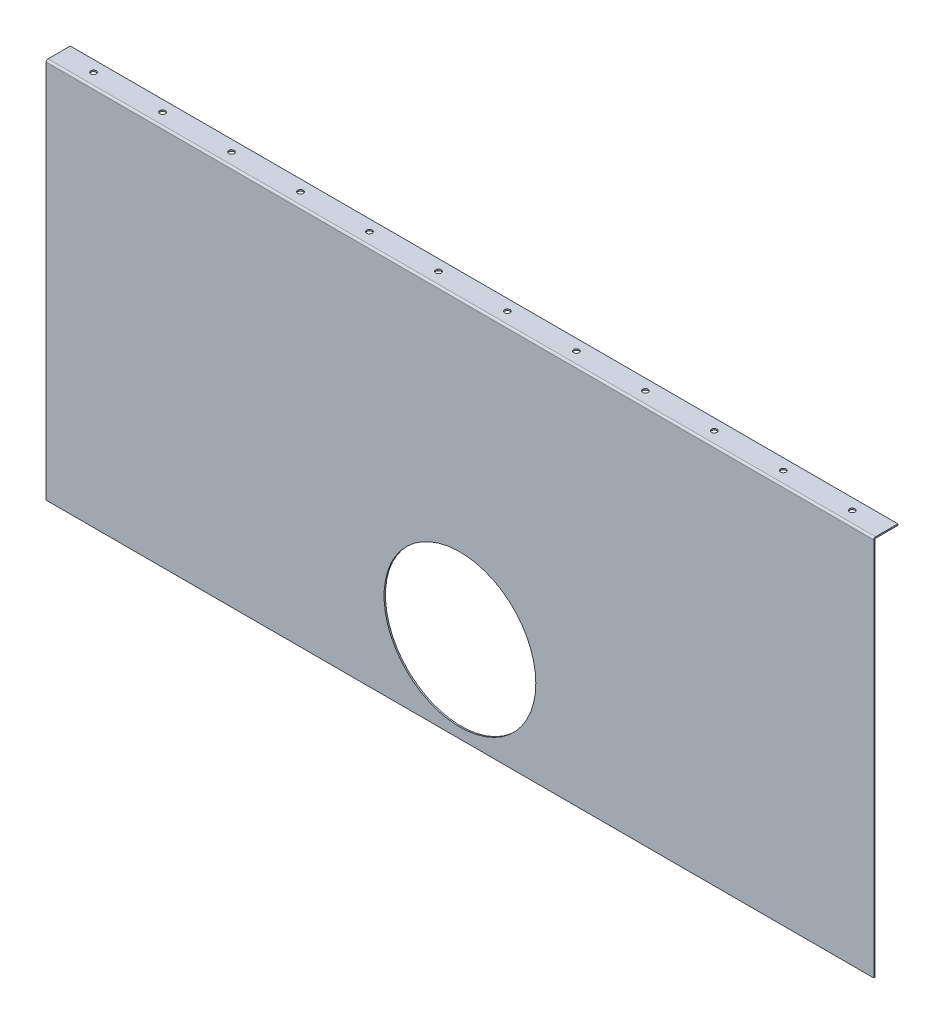
SolidWorks part; units mm, degrees
note: The reader was unsure of these and kept them because the rebuilt part matched: thickness of "Base-Flange1", "Edge-Flange1", "Sheet-Metal1", "Sheet-Metal2", "Sheet-Metal3", "Sheet-Metal4"; flange length of "Edge-Flange1".
material "AISI 304"
ref_plane "Front Plane" through (0, 0, 0) normal (0, 0, 1) x (1, 0, 0)
ref_plane "Top Plane" through (0, 0, 0) normal (0, 1, 0) x (1, 0, 0)
ref_plane "Right Plane" through (0, 0, 0) normal (1, 0, 0) x (0, 0, -1)
sketch "Sketch1" plane through (0, 0, 0) normal (0, 0, 1) x (1, 0, 0)
  line L1 (600, -275) -> (-600, -275)
  line L2 (600, -275) -> (600, 275)
  line L3 (600, 275) -> (-600, 275)
  line L4 (-600, -275) -> (-600, 275)
  line L5 (600, -275) -> (-600, 275) construction
  line L6 (600, 275) -> (-600, -275) construction
  point P0 (0, 0)
  dimension "D1" = 1200
  dimension "D2" = 550
base flange "Base-Flange1" sketch "Sketch1" thickness 2 reverse thickness direction no parameters "D1"=0.7366
edge flange "Edge-Flange1" sketch "Sketch8" flange angle 90 flange length 35 flange position bend outside bend radius 0.7366 thickness 2 relief rectangular parameters "D6"=10
sketch "Sketch8" plane through (0, 275, -2) normal (0, -1, 0) x (-1, 0, 0)
  line L2 (-600, 0) -> (-600, 33)
  line L3 (-600, 33) -> (600, 33)
  line L4 (600, 33) -> (600, 0)
  line L5 (600, 0) -> (-600, 0) construction
  line L6 (600, 0) -> (-600, 0)
bend "EdgeBend1" bend radius 0.7366 bend angle 90 parameters "D5"=1
sketch "Sketch9" plane through (0, 275.7366, 0) normal (0, -1, 0) x (1, 0, 0)
  line L0 (-600, -18.8683) -> (-550, -18.8683) construction
  line L1 (-600, -2.7366) -> (-600, -35) construction
  line L2 (550, -18.8683) -> (600, -18.8683) construction
  line L3 (600, -35) -> (600, -2.7366) construction
  circle A0 centre (-550, -18.8683) radius 4
  circle A1 centre (-450, -18.8683) radius 4
  circle A2 centre (-350, -18.8683) radius 4
  circle A3 centre (-250, -18.8683) radius 4
  circle A4 centre (-150, -18.8683) radius 4
  circle A5 centre (-50, -18.8683) radius 4
  circle A6 centre (50, -18.8683) radius 4
  circle A7 centre (150, -18.8683) radius 4
  circle A8 centre (250, -18.8683) radius 4
  circle A9 centre (350, -18.8683) radius 4
  circle A10 centre (450, -18.8683) radius 4
  circle A11 centre (550, -18.8683) radius 4
  dimension "D1" = 8
  dimension "D3" = 100
  dimension "D2" = 12
extrude "Cut-Extrude1" cut sketch "Sketch9" against normal blind 10
sketch "Sketch10" plane through (0, 0, 0) normal (0, 0, 1) x (1, 0, 0)
  line L0 (0, -260) -> (0, -275) construction
  line L1 (-600, -275) -> (600, -275) construction
  circle A0 centre (0, -150) radius 110
  dimension "D1" = 220
  dimension "D2" = 15
extrude "Cut-Extrude2" cut sketch "Sketch10" against normal blind 10
sketch "Bend-Lines1" [suppressed] plane through (0, 0, 0) normal (0, 1, 0) x (1, 0, 0)
sketch "Bounding-Box1" [suppressed] plane through (0, 0, 0) normal (0, 1, 0) x (1, 0, 0)
sheet metal parameters "Sheet-Metal1" thickness 2 parameters "D1"=0.7366
flat pattern "Flat-Pattern1" [suppressed]
sketch "Bend-Lines2" plane through (0, 0, 0) normal (0, 1, 0) x (1, 0, 0)
sketch3d "Bounding-Box2" [suppressed]
  line L0 (600, -250, 0) -> (-600, -250, 0) construction
  line L1 (600, 250, 0) -> (-600, 250, 0) construction
  line L2 (600, -250, 0) -> (600, 250, 0) construction
  line L3 (-600, -250, 0) -> (-600, 250, 0) construction
sheet metal parameters "Sheet-Metal2" thickness 2 parameters "D1"=0.7366, "D7"=3
flat pattern "Flat-Pattern1"
sketch "Bend-Lines2" plane through (0, 0, 0) normal (0, 0, 1) x (1, 0, 0)
  line L0 (600, 251.3639) -> (-600, 251.3639) construction
  line L1 (600, 251.3639) -> (-600, 251.3639) construction
sketch3d "Bounding-Box2" [suppressed]
  line L0 (-600, -250, 0) -> (600, -250, 0) construction
  line L1 (-600, 284.9912, 0) -> (600, 284.9912, 0) construction
  line L2 (-600, -250, 0) -> (-600, 284.9912, 0) construction
  line L3 (600, -250, 0) -> (600, 284.9912, 0) construction
bend of the flat pattern "Flatten-<EdgeBend1>1"
sheet metal parameters "Sheet-Metal3" thickness 2 parameters "D1"=0.7366, "D7"=3
flat pattern "Flat-Pattern1"
sketch "Bend-Lines2" plane through (0, 0, 0) normal (0, 0, 1) x (1, 0, 0)
  line L0 (600, 276.3639) -> (-600, 276.3639) construction
  line L1 (600, 276.3639) -> (-600, 276.3639) construction
sketch3d "Bounding-Box2" [suppressed]
  line L0 (-600, -275, 0) -> (600, -275, 0) construction
  line L1 (-600, 309.9912, 0) -> (600, 309.9912, 0) construction
  line L2 (-600, -275, 0) -> (-600, 309.9912, 0) construction
  line L3 (600, -275, 0) -> (600, 309.9912, 0) construction
bend of the flat pattern "Flatten-<EdgeBend1>1"
sheet metal parameters "Sheet-Metal4" thickness 2 parameters "D1"=0.7366, "D7"=3
flat pattern "Flat-Pattern1"
sketch "Bend-Lines2" plane through (0, 0, 0) normal (0, 0, 1) x (1, 0, 0)
  line L0 (600, 276.3639) -> (-600, 276.3639) construction
  line L1 (600, 276.3639) -> (-600, 276.3639) construction
sketch3d "Bounding-Box2" [suppressed]
  line L0 (-600, -275, 0) -> (600, -275, 0) construction
  line L1 (-600, 309.9912, 0) -> (600, 309.9912, 0) construction
  line L2 (-600, -275, 0) -> (-600, 309.9912, 0) construction
  line L3 (600, -275, 0) -> (600, 309.9912, 0) construction
bend of the flat pattern "Flatten-<EdgeBend1>1"
equation "\"thickness 1\" = 2"
equation "\"thickness 2\"= 3"
equation "\"connecting flange\"= 35"
equation "\"main length\"= 1200"
equation "\"main width\"= 1200"
equation "\"divider panel distance offset\"= 296"
equation "\"side panel length\"= 1200"
equation "\"side panel width\"= 950"
equation "\"access hatch length\" = \"access hatch cutout length\" + \"access hatch offset\" * 2"
equation "\"access hatch width\" = \"access hatch cutout width\" + \"access hatch offset\" * 2"
equation "\"access hatch offset X\"= 100"
equation "\"access hatch offset Y\"= 100"
equation "\"back panel access hatch length\"= 1150"
equation "\"back panel access hatch width\"= 206"
equation "\"back panel access hatch flange\"= 40"
equation "\"slotted panel length\" = \"main length\" + 100"
equation "\"slotted panel width\" = \"main width\""
equation "\"slot count x\"= 4"
equation "\"slot count y\"= 9"
equation "\"slot offset\" = \"water tray depth\""
equation "\"slot length\"= 30"
equation "\"slot width\"= 200"
equation "\"slot offset x\" = \"slot length\" + \"slot offset\""
equation "\"slot offset y\" = \"slot width\" + \"slot offset\""
equation "\"drift eliminator size offset\"= 5"
equation "\"drift eliminator length\"= \"back panel access hatch length\" - \"drift eliminator size offset\""
equation "\"drift eliminator width\"= \"back panel access hatch width\" - \"drift eliminator size offset\""
equation "\"drift eliminator depth\" = \"divider panel distance offset\""
equation "\"guide rail flange\"= 40"
equation "\"guid rail flange mount side\"= 20"
equation "\"guid rail back length\" = \"main width\" - \"guide rail flange\" * 2"
equation "\"splash plate length\"= 400"
equation "\"splash plate width\" = \"main width\""
equation "\"splash plate air gap\"= 200"
equation "\"splash plate slot count\"= 11"
equation "\"splash plate slot length\"= 50"
equation "\"splash plate slot height\"= 50"
equation "\"splash plate slot offset\"= 65"
equation "\"water tray depth\"= 150"
equation "\"water tray width\"= 200"
equation "\"dimpled panel length\" = \"main length\" - 200 - \"water tray depth\"/2"
equation "\"dimpled panel top offset\" = \"water tray depth\"/2"
equation "\"dimpled panel width\" = \"main width\""
equation "\"dimple panel slot count\"= 36"
equation "\"dimple panel slot length\"= 8"
equation "\"dimple panel slot width\"= 8"
equation "\"dimple panel slot offset\"= 25"
equation "\"sump base flat section width\"= 300"
equation "\"sump upper depth\"= 300"
equation "\"sump depth\"= 550"
equation "\"D1@Sketch1\"=\"main width\""
equation "\"D2@Sketch1\"=\"sump depth\""
equation "\"D7@Edge-Flange1\"=\"connecting flange\""
equation "\"D7@Sheet-Metal1\"=\"thickness 1\""
equation "\"thickness radius 1\"= 3.7366"
equation "\"connecting flange holes\"= 8"
equation "\"connecting flange hole gap\"= 100"
equation "\"top panel slot length\"= 250"
equation "\"top panel slot width\"= 700"
equation "\"water tray panel length\"= 473"
equation "\"leg length\" = \"sump depth\" + 150"
equation "\"leg width\"= 80"
equation "\"leg depth\"= 40"
equation "\"leg support plate size\" = \"leg width\" - \"thickness 2\" * 2"
equation "\"leg base plate thickness\"= 8"
equation "\"D1@Sketch9\"=\"connecting flange holes\""
equation "\"D3@Sketch9\"=\"connecting flange hole gap\""
